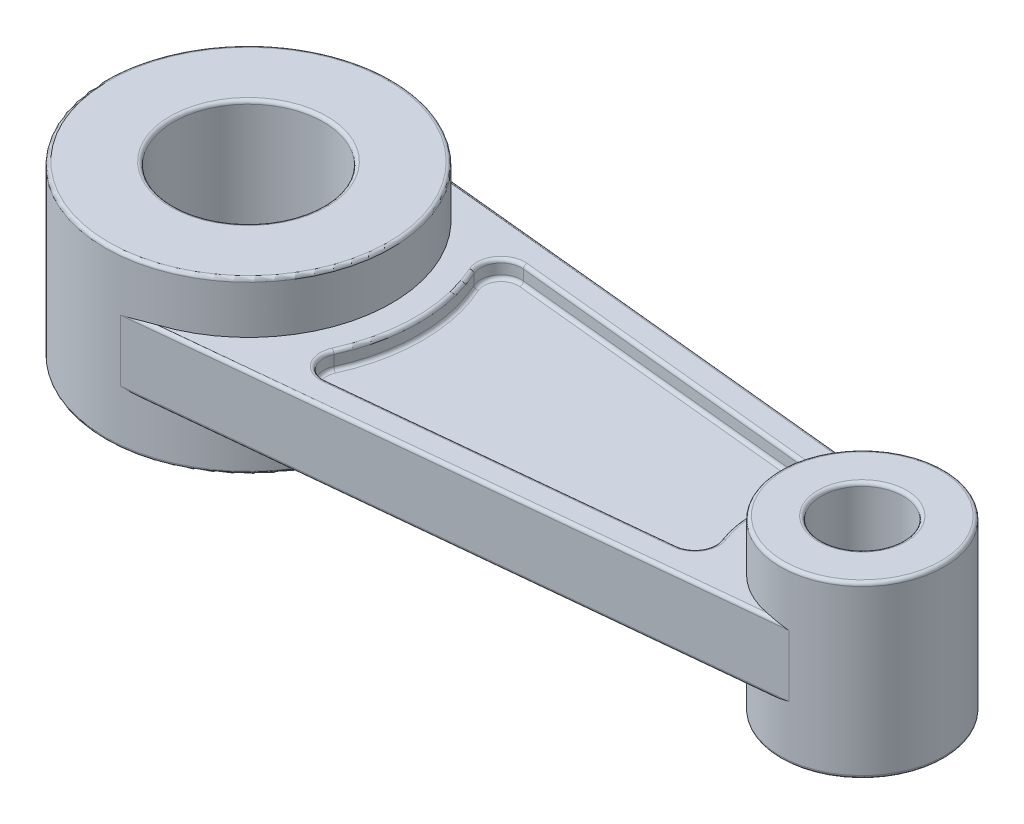
SolidWorks part; units mm, degrees
ref_plane "Front Plane" through (0, 0, 0) normal (0, 0, 1) x (1, 0, 0)
ref_plane "Top Plane" through (0, 0, 0) normal (0, 1, 0) x (1, 0, 0)
ref_plane "Right Plane" through (0, 0, 0) normal (1, 0, 0) x (0, 0, -1)
sketch "Sketch1" plane through (0, 0, 0) normal (0, 1, 0) x (1, 0, 0)
  circle A0 centre (0, 0) radius 21
  dimension "D1" = 42
extrude "Boss-Extrude1" add sketch "Sketch1" along normal mid plane 25
sketch "Sketch2" plane through (0, 12.5, 0) normal (0, 1, 0) x (1, 0, 0)
  circle A0 centre (0, 0) radius 11
  dimension "D1" = 22
extrude "Cut-Extrude1" cut sketch "Sketch2" against normal blind 25
sketch "Sketch3" plane through (0, 12.5, 0) normal (0, 1, 0) x (1, 0, 0)
  line L0 (0, 0) -> (90, 0) construction
  circle A0 centre (90, 0) radius 12
  dimension "D1" = 24
  dimension "D2" = 90
extrude "Boss-Extrude2" add sketch "Sketch3" against normal blind 25 separate body
sketch "Sketch4" plane through (0, 12.5, 0) normal (0, 1, 0) x (1, 0, 0)
  circle A0 centre (90, 0) radius 6
  dimension "D1" = 12
extrude "Cut-Extrude2" cut sketch "Sketch4" against normal blind 25
sketch "Sketch8" plane through (0, 0, 0) normal (0, 1, 0) x (1, 0, 0)
  line L0 (2.1, 20.8947) -> (91.2, 11.9398)
  line L1 (2.1, -20.8947) -> (91.2, -11.9398)
  circle A0 centre (0, 0) radius 21 construction
  circle A1 centre (90, 0) radius 12 construction
  arc A2 (2.1, -20.8947) -> (2.1, 20.8947) centre (0, 0) ccw
  arc A3 (91.2, 11.9398) -> (91.2, -11.9398) centre (90, 0) ccw
  point P8 (0, 0)
extrude "Boss-Extrude3" add sketch "Sketch8" along normal mid plane 10 contours L0 A3 L1 A2
sketch "Sketch9" plane through (0, 5, 0) normal (0, 1, 0) x (1, 0, 0)
  line L4 (25.8272, 14.4899) -> (72.5616, 9.7929)
  line L5 (25.8272, -14.4899) -> (72.5616, -9.7929)
  line L6 (2.1, 20.8947) -> (91.2, 11.9398) construction
  line L7 (2.1, -20.8947) -> (91.2, -11.9398) construction
  arc A4 (75.0624, 5.733) -> (75.0624, -5.733) centre (90, 0) ccw
  arc A5 (22.7921, -10.2723) -> (22.7921, 10.2723) centre (0, 0) ccw
  arc A6 (91.2, 11.9398) -> (91.2, -11.9398) centre (90, 0) ccw construction
  arc A7 (25.8272, -14.4899) -> (22.7921, -10.2723) centre (25.5272, -11.505) cw
  circle A8 centre (0, 0) radius 21 construction
  arc A9 (75.0624, -5.733) -> (72.5616, -9.7929) centre (72.2616, -6.808) cw
  arc A10 (72.5616, 9.7929) -> (75.0624, 5.733) centre (72.2616, 6.808) cw
  arc A11 (25.8272, 14.4899) -> (22.7921, 10.2723) centre (25.5272, 11.505) ccw
  point P24 (0, 0)
  dimension "D2" = 3
  dimension "D4" = 4
  dimension "D5" = 4
  dimension "D1" = 4
  dimension "D3" = 4
extrude "Cut-Extrude3" cut sketch "Sketch9" against normal blind 2.5 contours A5 A11 L4 A10 A4 A9 L5 A7
mirror "Mirror1" about plane through (0, 0, 0) normal (0, 1, 0) of "Cut-Extrude3"
fillet "Fillet1" radius 0.5 12 edges at (0, -12.5, 11) (90, -12.5, 6) (90, -12.5, 12) (0, -12.5, 21) (46.65, -5, -16.4173) (46.65, 5, -16.4173) (46.65, -5, 16.4173) (46.65, 5, 16.4173) (90, 12.5, 12) (90, 12.5, 6) (0, 12.5, 11) (0, 12.5, 21)
fillet "Fillet2" radius 0.5 32 edges at (23.0921, 5, 13.2572) (25, 5, 0) (23.0921, 5, -13.2572) (49.1944, 5, -12.1414) (74.8159, 5, -8.3814) (74, 5, 0) (74.8159, 5, 8.3814) (49.1944, 5, 12.1414) (25, 2.5, 0) (23.0921, 2.5, -13.2572) (49.1944, 2.5, -12.1414) (74.8159, 2.5, -8.3814) (74, 2.5, 0) (74.8159, 2.5, 8.3814) (49.1944, 2.5, 12.1414) (23.0921, 2.5, 13.2572) (23.0921, -5, 13.2572) (49.1944, -5, 12.1414) (74.8159, -5, 8.3814) (74, -5, 0) (74.8159, -5, -8.3814) (49.1944, -5, -12.1414) (23.0921, -5, -13.2572) (25, -5, 0) (49.1944, -2.5, 12.1414) (74.8159, -2.5, 8.3814) (74, -2.5, 0) (74.8159, -2.5, -8.3814) (49.1944, -2.5, -12.1414) (23.0921, -2.5, -13.2572) (25, -2.5, 0) (23.0921, -2.5, 13.2572)
